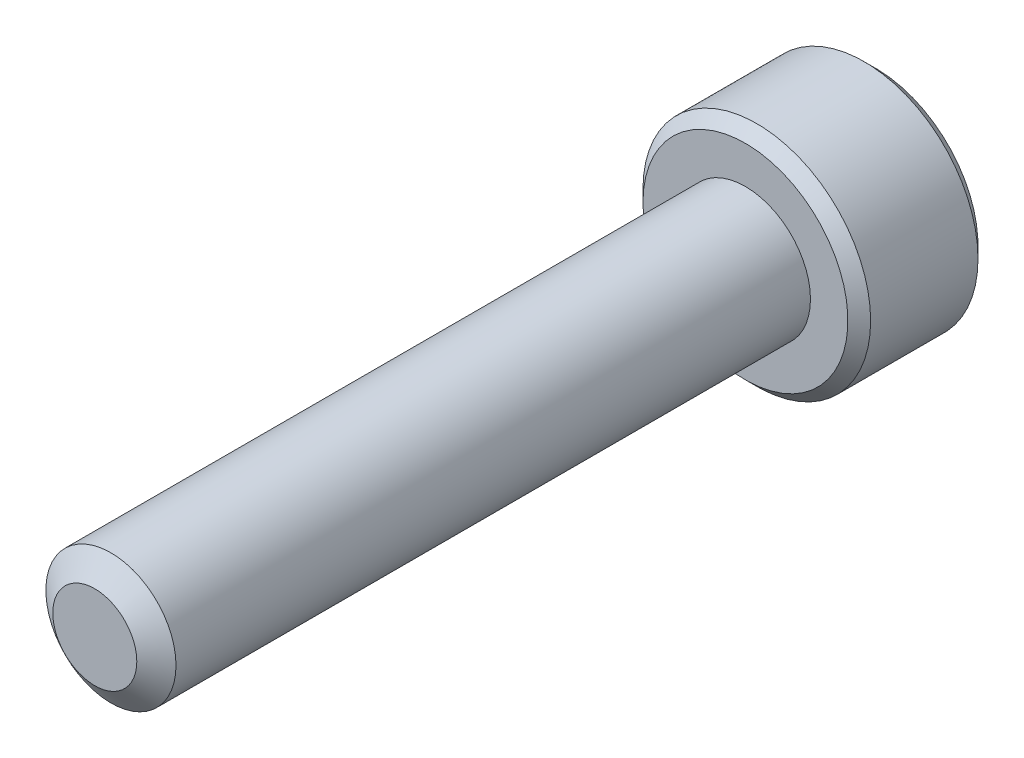
SolidWorks part; units mm, degrees
other "DetailItem1"
material "1.4310 (X10CrNi18-8)"
ref_plane "Front Plane" through (0, 0, 0) normal (0, 0, 1) x (1, 0, 0)
ref_plane "Top Plane" through (0, 0, 0) normal (0, 1, 0) x (1, 0, 0)
ref_plane "Right Plane" through (0, 0, 0) normal (1, 0, 0) x (0, 0, -1)
sketch "Sketch1" plane through (0, 0, 0) normal (0, 0, 1) x (1, 0, 0)
  circle A0 centre (0, 0) radius 2
  dimension "OD" = 4
extrude "Extrude1" add sketch "Sketch1" against normal blind 20
sketch "Sketch2" plane through (0, 0, 0) normal (0, 0, 1) x (1, 0, 0)
  circle A0 centre (0, 0) radius 2 construction
  circle A1 centre (0, 0) radius 2
curve "Helix/Spiral1" pitch 0.7 height 20.7 turns 29.5714 parameters "pitch"=0.7
sketch "Sketch3" plane through (0, 0, 0) normal (1, 0, 0) x (0, 0, -1)
  line L0 (-0.6125, 2) -> (-0.35, 1.5453)
  line L1 (-0.35, 1.5453) -> (-0.2625, 1.5453)
  line L2 (-0.2625, 1.5453) -> (0, 2)
  line L3 (-0.6125, 2) -> (0, 2)
  line L4 (-0.3062, 2) -> (-0.3062, 1.5453) construction
  line L5 (-0.4812, 1.7727) -> (-0.1312, 1.7727) construction
  line L6 (0, 2) -> (0, -2) construction
  dimension "D1" = 0.0875
  dimension "D2" = 0.35
  dimension "D3" = 60
sweep "Cut-Sweep1" [suppressed] cut profiles "Sketch3" path "Helix/Spiral1"
sketch "Sketch4" plane through (0, 0, 0) normal (1, 0, 0) x (0, 0, -1)
  line L0 (0.4962, 2) -> (0, 1.2913)
  line L1 (0, 1.2913) -> (0, 2)
  line L2 (0.4962, 2) -> (0, 2)
  line L3 (-0.6125, 2) -> (0, 2) construction
  line L4 (0, 0) -> (7.0209, 0) construction
  dimension "D1" = 55
  dimension "D2" = 0.254
revolve "Cut-Revolve1" cut sketch "Sketch4" angle 360 about L4
sketch "Sketch6" plane through (0, 0, -20) normal (0, 0, -1) x (-1, 0, 0)
  circle A0 centre (0, 0) radius 3.5
  dimension "head dia" = 7
extrude "Extrude2" add sketch "Sketch6" along normal blind 4
sketch "Sketch7" plane through (0, 0, -24) normal (0, 0, -1) x (-1, 0, 0)
  line L1 (0, 1.7321) -> (-1.5, 0.866)
  line L2 (-1.5, 0.866) -> (-1.5, -0.866)
  line L3 (-1.5, -0.866) -> (0, -1.7321)
  line L4 (0, -1.7321) -> (1.5, -0.866)
  line L5 (1.5, -0.866) -> (1.5, 0.866)
  line L6 (1.5, 0.866) -> (0, 1.7321)
  circle A0 centre (0, 0) radius 1.5 construction
  dimension "hex dia" = 3
extrude "Cut-Extrude1" cut sketch "Sketch7" against normal blind 2.25
sketch "Sketch8" plane through (0, 0, -24) normal (0, 0, -1) x (-1, 0, 0)
  circle A0 centre (0, 0) radius 1.7321
extrude "Cut-Extrude2" cut sketch "Sketch8" against normal through all draft 45
chamfer "Chamfer1" distance 0.35 angle 45 2 edges at (-3.5, 0, -24) (-3.5, 0, -20)
sketch "Sketch10" plane through (0, 0, -20) normal (0, 0, 1) x (1, 0, 0)
  circle A1 centre (0, 0) radius 2
  circle A2 centre (0, 0) radius 2
  dimension "D1" = 0
ref_plane "Plane1" through (0, 0, 0) normal (0, 0, 1) x (1, 0, 0)
extrude "partial thread" [suppressed] add sketch "Sketch10" along normal up to surface (10 mm away) separate body up to plane "Plane1"
chamfer "Chamfer2" [suppressed] distance 0.08 angle 45
combine bodies "Combine1" [suppressed] operation type add bodies to combine 107 108
sketch "Sketch9" plane through (0, 0, 0) normal (1, 0, 0) x (0, 0, -1)
  line L0 (0, 2) -> (0, -2) construction
  line L1 (1.75, 2) -> (1.75, -2) construction
  dimension "D1" = 1.75
equation "\"D3@Helix/Spiral1\" = \"screw length@Extrude1\"+\"pitch@Helix/Spiral1\""
equation "\"D1@Sketch3\" = \"pitch@Helix/Spiral1\"*.125"
equation "\"D2@Sketch3\" = \"pitch@Helix/Spiral1\"*.5"
equation "\"D1@Cut-Extrude1\" = \"hex dia@Sketch7\"*.75"
equation "\"D1@Chamfer1\" = \"head dia@Sketch6\"*.05"
equation "\"D1@Sketch9\" = \"pitch@Helix/Spiral1\"*2.5"
equation "\"D1@Chamfer2\"=\"OD@Sketch1\"*.02"
